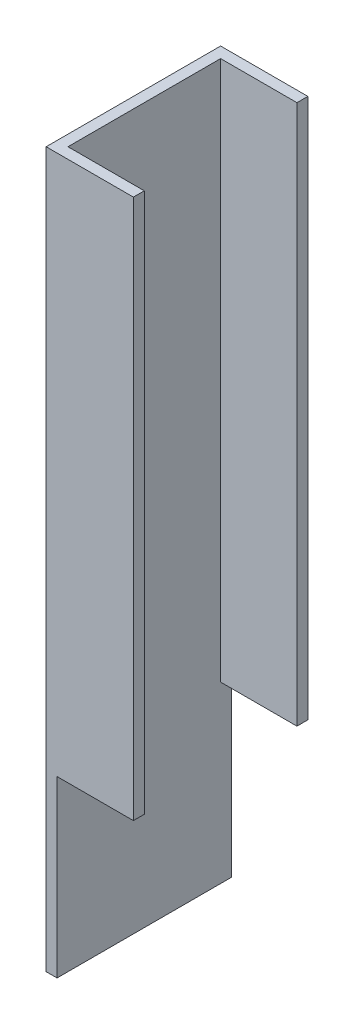
SolidWorks part; units mm, degrees
ref_plane "Front Plane" through (0, 0, 0) normal (0, 0, 1) x (1, 0, 0)
ref_plane "Top Plane" through (0, 0, 0) normal (0, 1, 0) x (1, 0, 0)
ref_plane "Right Plane" through (0, 0, 0) normal (1, 0, 0) x (0, 0, -1)
sketch "Sketch1" plane through (0, 0, 0) normal (0, 1, 0) x (1, 0, 0)
  line L0 (-20.955, 0) -> (-20.955, 25.4)
  line L1 (-20.955, 25.4) -> (4.445, 25.4)
  line L2 (4.445, 25.4) -> (4.445, 22.225)
  line L3 (4.445, 22.225) -> (-17.78, 22.225)
  line L4 (-17.78, 22.225) -> (-17.78, -22.225)
  line L5 (-17.78, -22.225) -> (4.445, -22.225)
  line L6 (4.445, -22.225) -> (4.445, -25.4)
  line L7 (4.445, -25.4) -> (-20.955, -25.4)
  line L8 (-20.955, -25.4) -> (-20.955, 0)
  dimension "D1" = 3.175
  dimension "D2" = 3.175
  dimension "D3" = 3.175
  dimension "D4" = 25.4
  dimension "D5" = 25.4
  dimension "D6" = 25.4
  dimension "D7" = 25.4
extrude "Boss-Extrude1" add sketch "Sketch1" along normal mid plane 208.026
sketch "Sketch2" plane through (0, 0, 25.4) normal (0, 0, 1) x (1, 0, 0)
  line L0 (-17.78, -104.013) -> (-17.78, -53.213)
  line L1 (-20.955, -104.013) -> (4.445, -104.013) construction
  line L2 (-17.78, -53.213) -> (4.445, -53.213)
  line L3 (4.445, 104.013) -> (4.445, -104.013) construction
  line L4 (4.445, -53.213) -> (4.445, -104.013)
  line L5 (4.445, -104.013) -> (-17.78, -104.013)
  line L6 (-20.955, 104.013) -> (-20.955, -104.013) construction
  dimension "D1" = 3.175
  dimension "D2" = 22.225
  dimension "D3" = 50.8
extrude "Cut-Extrude1" cut sketch "Sketch2" against normal blind 208.026
